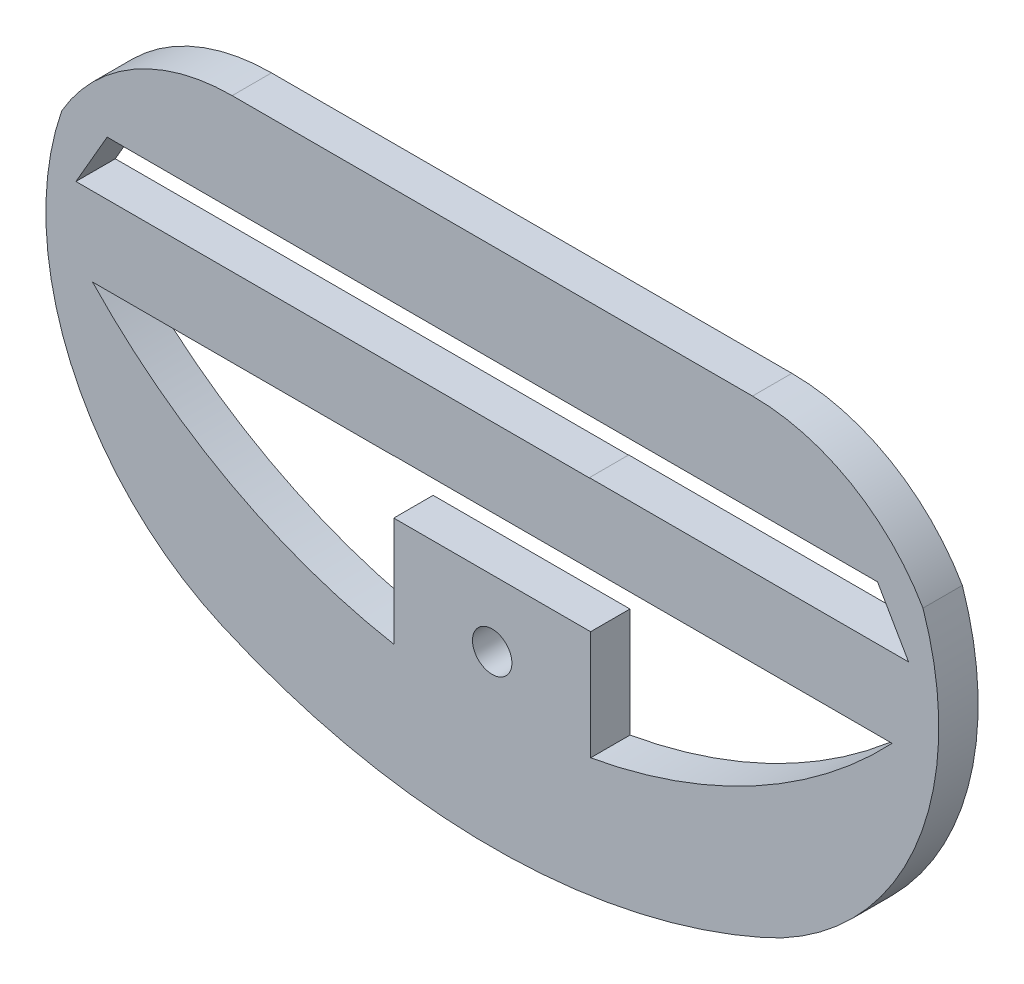
SolidWorks part; units mm, degrees
ref_plane "Front Plane" through (0, 0, 0) normal (0, 0, 1) x (1, 0, 0)
ref_plane "Top Plane" through (0, 0, 0) normal (0, 1, 0) x (1, 0, 0)
ref_plane "Right Plane" through (0, 0, 0) normal (1, 0, 0) x (0, 0, -1)
sketch "Sketch1" plane through (0, 0, 0) normal (0, 0, 1) x (1, 0, 0)
  line L0 (-65.8782, -12.4894) -> (70.819, -12.4894)
  line L1 (0, -33.96) -> (118.0317, -33.96)
  line L2 (0, -21.97) -> (0, -25.35)
  line L3 (5, -21.97) -> (-5, -21.97)
  line L4 (-5, -21.97) -> (-5, -33.96)
  line L5 (5, -21.97) -> (5, -31.4204)
  circle A0 centre (0, 0) radius 33.96
  arc A1 (-25.0267, -12.4894) -> (25.0267, -12.4894) centre (0, 0) ccw
  circle A2 centre (0, -25.35) radius 1
  point P13 (0, -21.97)
  dimension "D1" = 12.4894
extrude "Boss-Extrude1" add sketch "Sketch1" along normal blind 2 contours A1 L0 A0 L4 | A1 L4 A0 L0 | A2 L3 L4 A1 L5 region at (-18.2882, -23.5876, 0) region at (13.7861, -25.3701, 0) region at (-4.8834, -24.7447, 0)
sketch "Sketch2" plane through (0, 0, 2) normal (0, 0, 1) x (1, 0, 0)
  line L0 (-25.0267, -12.4894) -> (0, -12.4894)
  line L1 (0, -12.4894) -> (0, -21.97)
  line L2 (5, -21.97) -> (-5, -21.97) construction
  line L3 (-31.58, -12.4894) -> (31.58, -12.4894)
  line L4 (-31.58, -12.4894) -> (-31.58, -7.4894)
  line L5 (31.58, -12.4894) -> (31.58, -7.4894)
  line L6 (-31.58, -7.4894) -> (31.58, -7.4894)
  arc A0 (-31.58, -12.4894) -> (-29.2629, -7.4894) centre (-25.0267, -12.4894) cw
  arc A1 (31.58, -12.4894) -> (29.2629, -7.4894) centre (25.0267, -12.4894) ccw
  line M3 (-25.0267, -12.4894) -> (-31.58, -12.4894)
  line M5 (31.58, -12.4894) -> (25.0267, -12.4894)
extrude "Boss-Extrude2" add sketch "Sketch2" against normal blind 2 contours A1 L6 A0 L0 L3 M5 M3 region at (0, -10.0192, 2)
sketch "Sketch3" plane through (0, 0, 2) normal (0, 0, 1) x (1, 0, 0)
  line L0 (-5, -21.97) -> (-5, -12.4894)
  line L1 (-5, -21.97) -> (4.9375, -21.97)
  line L2 (-5, -12.4894) -> (4.9375, -12.4894)
  line L3 (4.9375, -21.97) -> (4.9375, -12.4894)
  line L4 (25.0267, -12.4894) -> (-25.0267, -12.4894) construction
  line L6 (14.9348, -19.2358) -> (-24.8138, -19.2358)
  line L8 (14.6935, -15.2358) -> (-24.8138, -15.2358)
  line L9 (-24.8138, -19.2358) -> (-24.8138, -15.2358)
  line L10 (14.9348, -19.2358) -> (-24.8138, -15.2358) construction
  line L11 (14.6935, -15.2358) -> (-24.8138, -19.2358) construction
  line L12 (-15.779, -15.2236) -> (25.5283, -15.2236)
  line L14 (-15.5283, -19.2236) -> (25.5283, -19.2236)
  line L15 (25.5283, -15.2236) -> (25.5283, -19.2236)
  line L16 (-15.779, -15.2236) -> (25.5283, -19.2236) construction
  line L17 (-15.5283, -19.2236) -> (25.5283, -15.2236) construction
  point P7 (-5, -17.2297)
  point P12 (4.9375, -17.2297)
  arc M8 (-5, -27.5195) -> (-25.0267, -12.4894) centre (0, 0) cw
  arc M10 (25.0267, -12.4894) -> (5, -27.5195) centre (0, 0) cw
extrude "Boss-Extrude3" add sketch "Sketch3" against normal blind 2 contours L0 L8 L6 M8 | L0 L14 L3 L8 | L3 L14 L12 M10 region at (-13.5139, -17.1741, 2) region at (-0.0312, -17.2297, 2) region at (13.4873, -17.1623, 2)
sketch "Sketch4" plane through (0, 0, 0) normal (0, 0, 1) x (1, 0, 0)
  line L0 (23.4641, -15.2236) -> (18.9987, -7.4894)
  line L1 (-29.2629, -7.4894) -> (29.2629, -7.4894) construction
  line L2 (18.9987, -7.4894) -> (26.7522, -20.9189)
  line L3 (26.7522, -20.9189) -> (23.4641, -15.2236)
  line L4 (23.4641, -15.2236) -> (17.8181, -15.2236)
  line L5 (4.9375, -15.2236) -> (23.4641, -15.2236) construction
  line L6 (18.9987, -7.4894) -> (26.7522, -20.9189)
  line L7 (18.9987, -7.4894) -> (17.2667, -8.4894)
  line L8 (26.7522, -20.9189) -> (25.0202, -21.9189)
  line L9 (17.2667, -8.4894) -> (25.0202, -21.9189)
  arc A0 (-31.58, -12.4894) -> (31.58, -12.4894) centre (0, 0) ccw construction
  dimension "D1" = 60
extrude "Boss-Extrude4" add sketch "Sketch4" along normal up to surface (2 mm away) contours L4 L9 L8 L2 | L7 L9 L4 L0 region at (20.2443, -11.6007, 0) region at (24.0706, -18.328, 0) up to face at (1.6471, -14.3236, 2)
sketch "Sketch6" plane through (0, 0, 0) normal (0, 0, -1) x (-1, 0, 0)
  line L0 (23.4562, -15.2358) -> (12.9484, -15.2358)
  line L1 (-4.9375, -15.2358) -> (23.4562, -15.2358) construction
  line L2 (23.4562, -15.2358) -> (16.4764, -3.1465)
  line L3 (22.9625, -14.3808) -> (23.4562, -15.2358)
  line L4 (23.4562, -15.2358) -> (26.7436, -20.9299)
  line L5 (26.7436, -20.9299) -> (18.9838, -7.4894)
  line L6 (29.2629, -7.4894) -> (-29.2629, -7.4894) construction
  line L7 (18.9838, -7.4894) -> (26.7436, -20.9299)
  line L8 (18.9838, -7.4894) -> (17.2517, -8.4894)
  line L9 (26.7436, -20.9299) -> (25.0116, -21.9299)
  line L10 (17.2517, -8.4894) -> (25.0116, -21.9299)
  arc A0 (-31.58, -12.4894) -> (31.58, -12.4894) centre (0, 0) ccw construction
  line M12 (-19.5761, -12.4894) -> (25.0267, -12.4894)
  line M14 (23.4562, -15.2358) -> (-4.9375, -15.2358)
  dimension "D1" = 60
extrude "Boss-Extrude6" add sketch "Sketch6" against normal up to surface (2 mm away) contours L10 L2 M12 M14 region at (-21.5087, -13.8626, 0) up to face at (0, -15.2294, 2)
sketch "Sketch7" plane through (0, 0, 0) normal (0, 0, -1) x (-1, 0, 0)
  line L1 (32.8835, -31.5643) -> (32.8835, -5.1489)
  line L2 (32.8835, -5.1489) -> (14.1066, -5.1489)
  line L3 (32.8835, -31.5643) -> (17.6325, -5.1489)
  line M4 (21.8705, -12.4894) -> (25.0267, -12.4894)
  arc M5 (25.0267, -12.4894) -> (23.4562, -15.2358) centre (0, 0) cw
  arc M8 (-31.58, -12.4894) -> (31.58, -12.4894) centre (0, 0) ccw
  arc M9 (31.58, -12.4894) -> (29.2629, -7.4894) centre (25.0267, -12.4894) ccw
  line M10 (29.2629, -7.4894) -> (-29.2629, -7.4894)
extrude "Cut-Extrude5" cut sketch "Sketch7" against normal blind 10 contours L3 M8 M9 M10 M4 M5 region at (-26.3264, -12.3681, 0)
sketch "Sketch8" plane through (0, 0, 0) normal (0, 0, -1) x (-1, 0, 0)
  line L0 (-23.4641, -15.2236) -> (-21.8855, -12.4894)
  line L1 (-21.8855, -12.4894) -> (-18.1983, -6.103)
  line L2 (-18.1983, -6.103) -> (-34.5293, -34.3892)
  line L3 (-34.5293, -34.3892) -> (-32.947, -6.103)
  line L4 (-32.947, -6.103) -> (-18.1983, -6.103)
  arc M11 (-23.4641, -15.2236) -> (-25.0267, -12.4894) centre (0, 0) cw
  line M12 (-25.0267, -12.4894) -> (-21.8855, -12.4894)
  arc M19 (-31.58, -12.4894) -> (26.7436, -20.9299) centre (0, 0) ccw
  line M21 (18.9838, -7.4894) -> (-29.2629, -7.4894)
  arc M22 (-29.2629, -7.4894) -> (-31.58, -12.4894) centre (-25.0267, -12.4894) ccw
extrude "Cut-Extrude6" cut sketch "Sketch8" against normal blind 10 contours L2 L1 M11 M12 M21 M22 M19 region at (26.3324, -12.3647, 0)
fillet "Fillet3" radius 10 2 edges at (-18.9838, -7.4894, 1) (18.9987, -7.4894, 1)
fillet "Fillet4" radius 15 2 edges at (26.7522, -20.9189, 1) (-26.7436, -20.9299, 1)
